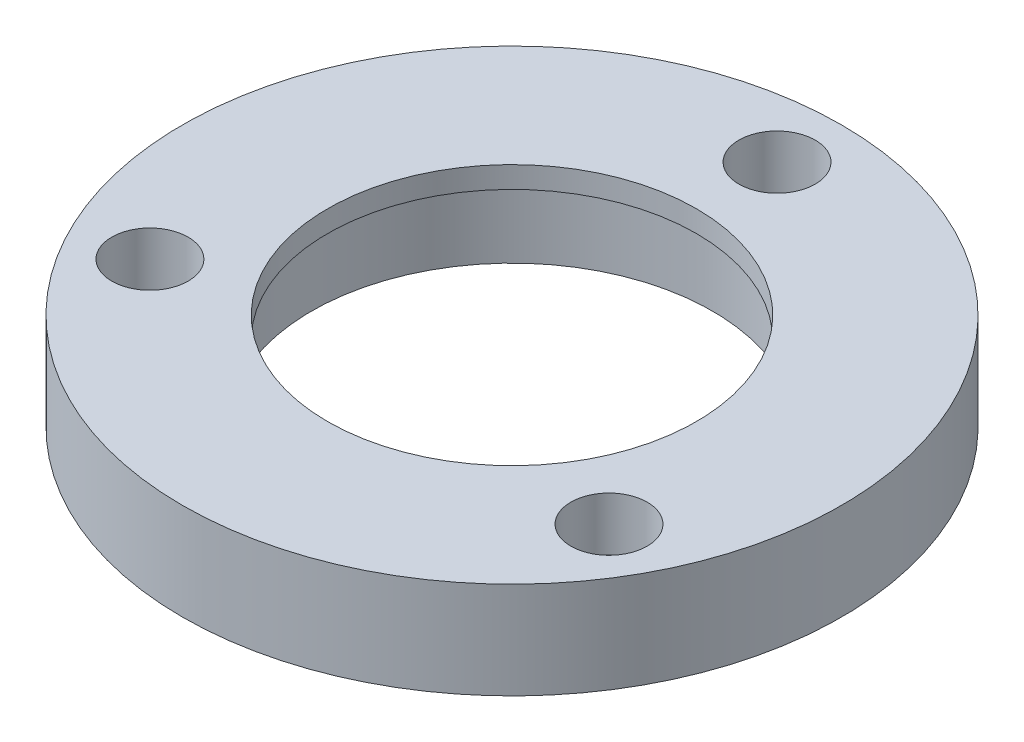
SolidWorks part; units mm, degrees
ref_plane "Спереди" through (0, 0, 0) normal (0, 0, 1) x (1, 0, 0)
ref_plane "Сверху" through (0, 0, 0) normal (0, 1, 0) x (1, 0, 0)
ref_plane "Справа" through (0, 0, 0) normal (1, 0, 0) x (0, 0, -1)
sketch "основа" plane through (0, 0, 0) normal (0, 0, 1) x (1, 0, 0)
  line L0 (0, 23.6626) -> (0, 0) construction
  line L1 (17.15, 9) -> (30.65, 9)
  line L2 (30.65, 9) -> (30.65, 0)
  line L3 (30.65, 0) -> (18.65, 0)
  line L4 (18.65, 0) -> (18.65, 7)
  line L5 (18.65, 7) -> (17.15, 7)
  line L6 (17.15, 7) -> (17.15, 9)
  dimension "D1" = 18.65
  dimension "D2" = 2
  dimension "D3" = 1.5
  dimension "D4" = 7
  dimension "D5" = 12
revolve "Повернуть1" add sketch "основа" angle 360 about L0
sketch "Эскиз2" plane through (0, 9, 0) normal (0, 1, 0) x (1, 0, 0)
  line L0 (0, 0) -> (0, 24.65) construction
  circle A0 centre (0, 0) radius 24.65
  circle A1 centre (0, 24.65) radius 2.25
  circle A2 centre (0, 24.65) radius 3.55
  circle A3 centre (21.3475, -12.325) radius 2.25
  circle A4 centre (21.3475, -12.325) radius 3.55
  circle A5 centre (-21.3475, -12.325) radius 2.25
  circle A6 centre (-21.3475, -12.325) radius 3.55
  dimension "D1" = 49.3
  dimension "D2" = 7.1
  dimension "D3" = 4.5
  dimension "D5" = 24.65
  dimension "D4" = 3
extrude "Отверстия" cut sketch "Эскиз2" against normal through all contours A1 | A5 | A3
extrude "Вырез под шляпки" cut sketch "Эскиз2<3>" against normal blind 5 contours L0 A2 A0 A1 | A0 A2 A1 | A2 L0 A1 A0 | A0 A4 A3 | A0 A4 A3 | A0 A6 A5 | A0 A6 A5 region at (-1.8329, 9, -22.7022) region at (1.8329, 9, -22.7022) region at (-0.125, 9, -28.1172) region at (-19.5067, 9, 9.3865) region at (-22.7276, 9, 9.7668) region at (24.282, 9, 10.4867) region at (22.5716, 9, 9.6998)
sketch "Эскиз2<3>" plane through (0, 9, 0) normal (0, 1, 0) x (1, 0, 0) same geometry as "Эскиз2"
